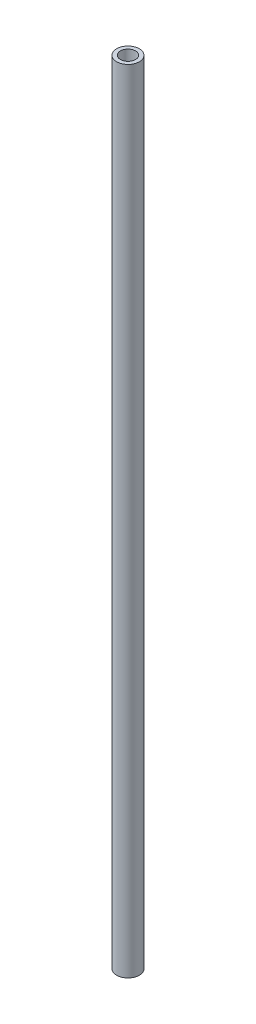
SolidWorks part; units mm, degrees
ref_plane "Front Plane" through (0, 0, 0) normal (0, 0, 1) x (1, 0, 0)
ref_plane "Top Plane" through (0, 0, 0) normal (0, 1, 0) x (1, 0, 0)
ref_plane "Right Plane" through (0, 0, 0) normal (1, 0, 0) x (0, 0, -1)
sketch "Sketch1" plane through (0, 0, 0) normal (0, 1, 0) x (1, 0, 0)
  circle A0 centre (0, 0) radius 2.54
  circle A1 centre (0, 0) radius 3.81
  dimension "D1" = 5.08
  dimension "D2" = 7.62
extrude "Boss-Extrude1" add sketch "Sketch1" along normal blind 266.7
